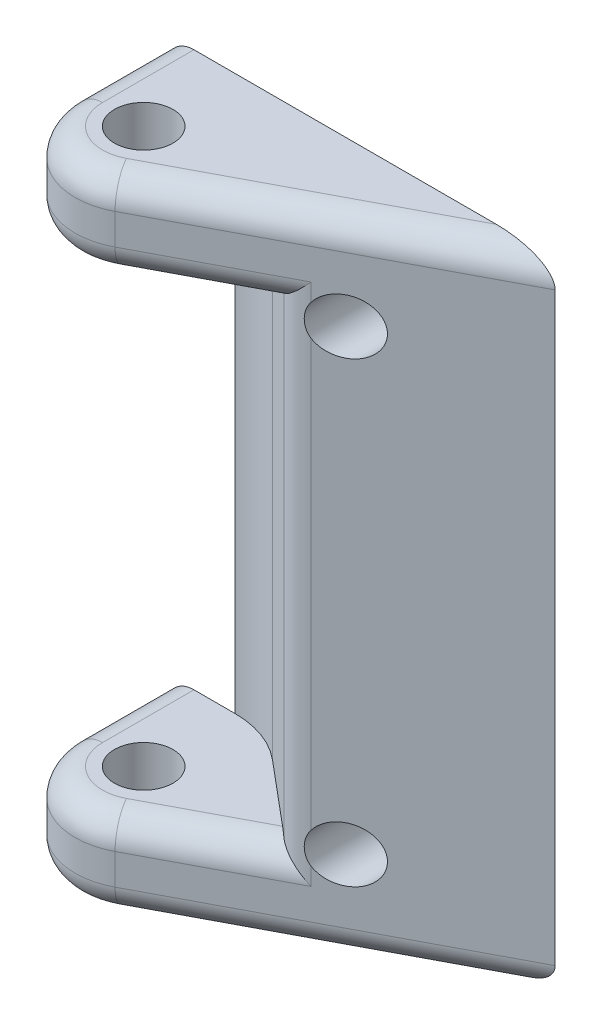
SolidWorks part; units mm, degrees
ref_plane "Front Plane" through (0, 0, 0) normal (0, 0, 1) x (1, 0, 0)
ref_plane "Top Plane" through (0, 0, 0) normal (0, 1, 0) x (1, 0, 0)
ref_plane "Right Plane" through (0, 0, 0) normal (1, 0, 0) x (0, 0, -1)
sketch "Sketch1" plane through (0, 0, 0) normal (0, 1, 0) x (1, 0, 0)
  line L2 (-4.7625, 6.35) -> (-4.7625, 0)
  line L3 (2.2238, -4.2114) -> (22.225, 6.35)
  line L4 (22.225, 6.35) -> (-4.7625, 6.35)
  circle A0 centre (0, 0) radius 2.032
  arc A1 (-4.7625, 0) -> (2.2238, -4.2114) centre (0, 0) ccw
  dimension "D1" = 4.064
  dimension "D2" = 22.225
  dimension "D4" = 4.7625
  dimension "D5" = 6.35
extrude "Boss-Extrude1" add sketch "Sketch1" along normal mid plane 44.45
sketch "Sketch6" plane through (0, 0, 0) normal (0, 1, 0) x (1, 0, 0)
  line L0 (0, 6.35) -> (-4.7625, 6.35)
  line L1 (-4.7625, 6.35) -> (-4.7625, 0) construction
  line L2 (-4.7625, 6.35) -> (-4.7625, 0)
  line L3 (4.0817, 4.8644) -> (10.0027, -0.1039)
  line L4 (2.2238, -4.2114) -> (22.225, 6.35) construction
  line L5 (10.0027, -0.1039) -> (2.2238, -4.2114)
  arc A0 (-4.7625, 0) -> (2.2238, -4.2114) centre (0, 0) ccw
  arc A2 (4.0817, 4.8644) -> (0, 6.35) centre (0, 0) ccw
  dimension "D1" = 6.35
  dimension "D2" = 140
extrude "Cut-Extrude4" cut sketch "Sketch6" against normal mid plane 32.5437
sketch "Sketch13" plane through (0, 0, -6.35) normal (0, 0, -1) x (-1, 0, 0)
  line L0 (-12.7, 15.875) -> (-12.7, -15.875) construction
  circle A0 centre (-12.7, 15.875) radius 1.905
  circle A1 centre (-12.7, -15.875) radius 1.905
  point P4 (-12.7, 0)
  dimension "D1" = 3.81
  dimension "D2" = 31.75
  dimension "D3" = 12.7
extrude "Cut-Extrude9" cut sketch "Sketch13" against normal through all
sketch "Sketch14" plane through (0, 0, -6.35) normal (0, 0, -1) x (-1, 0, 0)
  line L1 (-10.3536, 19.939) -> (-15.0464, 19.939)
  line L2 (-15.0464, 19.939) -> (-17.3927, 15.875)
  line L3 (-17.3927, 15.875) -> (-15.0464, 11.811)
  line L4 (-15.0464, 11.811) -> (-10.3536, 11.811)
  line L5 (-10.3536, 11.811) -> (-8.0073, 15.875)
  line L6 (-8.0073, 15.875) -> (-10.3536, 19.939)
  line L7 (-8.0073, -15.875) -> (-10.3536, -11.811)
  line L8 (-10.3536, -11.811) -> (-15.0464, -11.811)
  line L9 (-15.0464, -11.811) -> (-17.3927, -15.875)
  line L10 (-17.3927, -15.875) -> (-15.0464, -19.939)
  line L11 (-15.0464, -19.939) -> (-10.3536, -19.939)
  line L12 (-10.3536, -19.939) -> (-8.0073, -15.875)
  circle A0 centre (-12.7, 15.875) radius 4.064 construction
  circle A1 centre (-12.7, -15.875) radius 4.064 construction
  dimension "D1" = 8.128
  dimension "D2" = 8.128
extrude "Cut-Extrude10" [suppressed] cut sketch "Sketch14" against normal through all from offset 3.175 offset against normal yes
fillet "Fillet1" radius 1.905 13 edges at (-4.7625, -22.225, -3.175) (-2.4587, -22.225, 4.0787) (12.2244, 22.225, -1.0693) (-2.4587, 22.225, 4.0787) (12.2244, -22.225, -1.0693) (-4.7625, 22.225, -3.175) (-4.7625, -16.2719, -3.175) (6.1132, -16.2719, 2.1577) (-4.7625, 16.2719, -3.175) (-2.4587, 16.2719, 4.0787) (-2.4587, -16.2719, 4.0787) (6.1132, 16.2719, 2.1577) (10.0027, 0, 0.1039)
fillet "Fillet2" [suppressed] radius 0.0635
